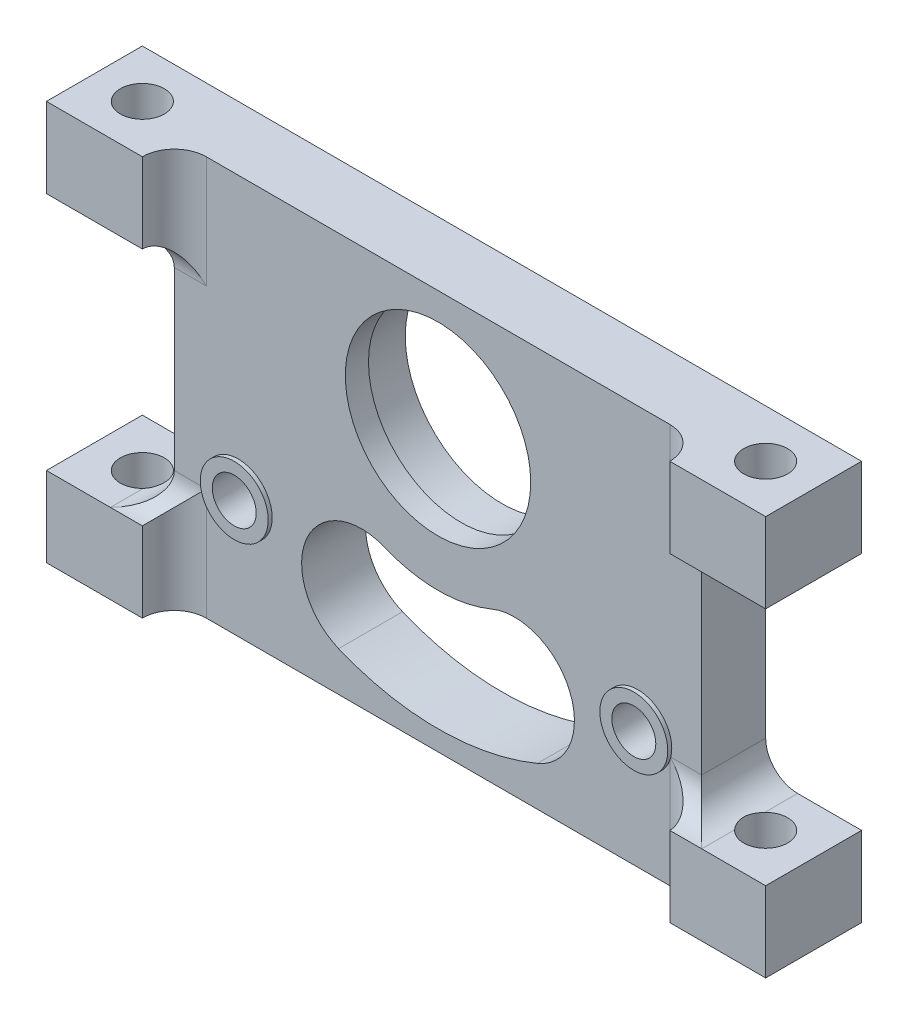
SolidWorks part; units mm, degrees
ref_plane "Front Plane" through (0, 0, 0) normal (0, 0, 1) x (1, 0, 0)
ref_plane "Top Plane" through (0, 0, 0) normal (0, 1, 0) x (1, 0, 0)
ref_plane "Right Plane" through (0, 0, 0) normal (1, 0, 0) x (0, 0, -1)
sketch "Sketch1" plane through (0, 0, 0) normal (0, 0, 1) x (1, 0, 0)
  line L1 (45, 50) -> (78, 50)
  line L2 (45, 50) -> (45, 0)
  line L3 (45, 0) -> (78, 0)
  line L4 (78, 50) -> (78, 0)
  line L7 (0, 0) -> (45, 0) construction
  dimension "D1" = 33
  dimension "D2" = 50
  dimension "D3" = 45
extrude "Boss-Extrude1" add sketch "Sketch1" along normal blind 8 separate body
sketch "Sketch2" plane through (0, 0, 0) normal (0, 0, -1) x (-1, 0, 0)
  line L1 (-90, 50) -> (-78, 50)
  line L2 (-90, 50) -> (-90, 40)
  line L3 (-90, 40) -> (-78, 40)
  line L4 (-78, 50) -> (-78, 40)
  line L5 (-45, 25) -> (-82.3085, 25) construction
  line L6 (-45, 50) -> (-45, 0) construction
  line L7 (-78, 0) -> (-78, 10)
  line L8 (-90, 10) -> (-78, 10)
  line L9 (-90, 0) -> (-90, 10)
  line L10 (-90, 0) -> (-78, 0)
  dimension "D1" = 12
  dimension "D2" = 10
extrude "Boss-Extrude2" add sketch "Sketch2" against normal blind 12
fillet "Fillet1" radius 4 2 edges at (78, 10, 4) (78, 40, 4)
fillet "Fillet2" radius 4 4 edges at (78, 5, 8) (80, 10, 8) (78, 45, 8) (80, 40, 8)
sketch "Sketch3" plane through (0, 0, 8) normal (0, 0, 1) x (1, 0, 0)
  line L0 (45, 50) -> (45, 0) construction
  line L1 (74, 50) -> (45, 50) construction
  line L2 (54.5671, 11.903) -> (45, 35) construction
  line L3 (27.5, 35) -> (12.5, 35)
  circle A0 centre (70, 15) radius 2.75
  circle A1 centre (45, 35) radius 11.6
  arc A2 (27.5, 35) -> (51.697, 18.8321) centre (45, 35) ccw
  arc A3 (12.5, 35) -> (57.4372, 4.9739) centre (45, 35) ccw
  arc A4 (57.4372, 4.9739) -> (51.697, 18.8321) centre (54.5671, 11.903) ccw
  dimension "D1" = 5.5
  dimension "D2" = 23.2
  dimension "D4" = 35
  dimension "D5" = 65
  dimension "D3" = 15
  dimension "D6" = 22.5
extrude "Cut-Extrude1" cut sketch "Sketch3" against normal through all
sketch "Sketch4" plane through (0, 0, 8) normal (0, 0, 1) x (1, 0, 0)
  circle A0 centre (70, 15) radius 2.75 construction
  circle A1 centre (70, 15) radius 2.75
  circle A2 centre (70, 15) radius 4.25
  dimension "D1" = 8.5
extrude "Boss-Extrude3" add sketch "Sketch4" along normal blind 0.5
sketch "Sketch7" plane through (0, 50, 0) normal (0, 1, 0) x (1, 0, 0)
  line L0 (84, -12) -> (84, 0) construction
  line L1 (78, -12) -> (90, -12) construction
  line L2 (90, 0) -> (45, 0) construction
  line L3 (78, -12) -> (78, 0) construction
  line L4 (78, -6) -> (90, -6) construction
  line L5 (90, -12) -> (90, 0) construction
  circle A0 centre (84, -6) radius 2.75
  dimension "D1" = 5.5
extrude "Cut-Extrude3" cut sketch "Sketch7" against normal through all
mirror "Mirror1" about plane through (45, 50, 8) normal (1, 0, 0) of bodies 108 105
sketch "Sketch6" plane through (0, 0, 0) normal (0, 0, -1) x (-1, 0, 0)
  circle A0 centre (-45, 35) radius 12.1
  dimension "D1" = 24.2
extrude "Cut-Extrude2" cut sketch "Sketch6" against normal blind 5.1
ref_plane "Mid Plane" through (45, 0, 0) normal (1, 0, 0) x (0, 0, -1)
chamfer "Chamfer1" distance 2.5 angle 45 2 edges at (72.75, 15, 0) (17.25, 15, 0)
